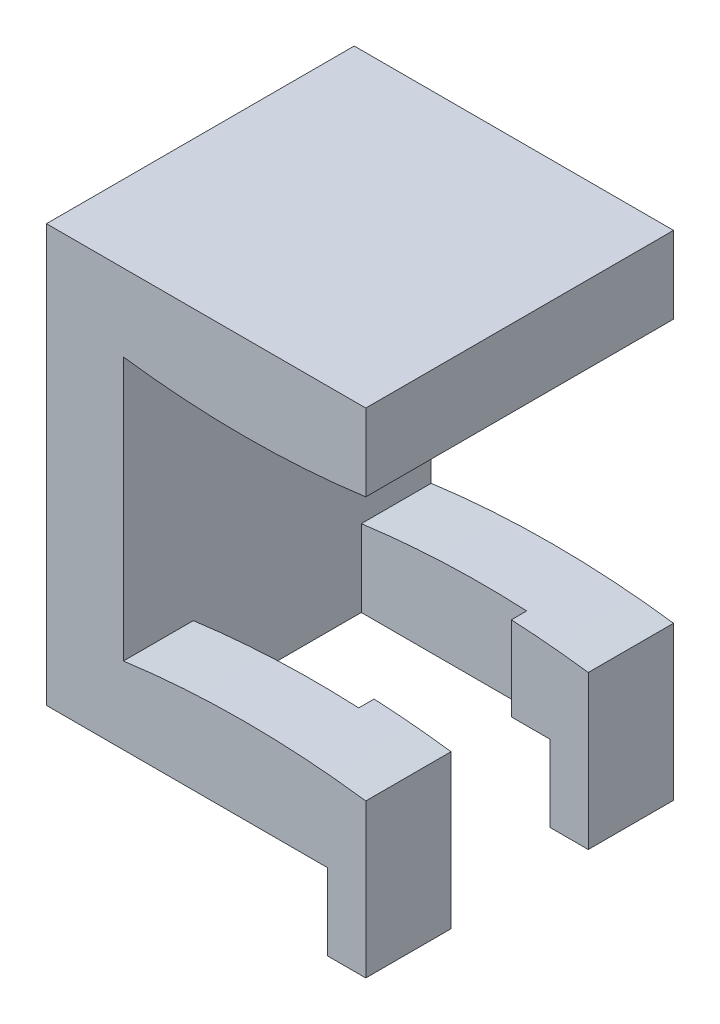
SolidWorks part; units mm, degrees
ref_plane "Front Plane" through (0, 0, 0) normal (0, 0, 1) x (1, 0, 0)
ref_plane "Top Plane" through (0, 0, 0) normal (0, 1, 0) x (1, 0, 0)
ref_plane "Right Plane" through (0, 0, 0) normal (1, 0, 0) x (0, 0, -1)
sketch "Sketch1" plane through (0, 0, 0) normal (0, 0, 1) x (1, 0, 0)
  line L2 (-159.7982, 8.1335) -> (-172.2482, 8.1335)
  line L3 (-172.2482, 8.1335) -> (-172.2482, -8.1335)
  line L7 (-169.2482, -22.8519) -> (-169.2482, 5.1335) construction
  line L12 (-169.2482, 4.7625) -> (-169.2482, 1.5875) construction
  line L23 (-159.7982, 5.1335) -> (-159.7982, 8.1335)
  line L28 (-164.5232, 4.8125) -> (-144.5007, 4.8125) construction
  line L29 (-156.5482, 4.7625) -> (-169.2482, 4.7625) construction
  line L30 (-169.2482, 5.1335) -> (-169.2482, 4.7625)
  line L32 (-158.1026, 4.7625) -> (-158.1026, -4.7625) construction
  line L33 (-169.2482, -4.7625) -> (-156.5482, -4.7625) construction
  line L34 (-169.2482, 4.7625) -> (-169.2482, -4.7625)
  line L35 (-172.2482, 0) -> (-169.2482, 0) construction
  line L36 (-169.2482, -5.1335) -> (-169.2482, -4.7625)
  line L37 (-159.7982, -5.1335) -> (-159.7982, -8.1335)
  line L38 (-159.7982, -8.1335) -> (-172.2482, -8.1335)
  line L39 (-159.7982, 4.7625) -> (-159.7982, 1.5875) construction
  arc A5 (-169.2482, 5.1335) -> (-159.7982, 5.1335) centre (-164.5232, 39.752) ccw
  arc A6 (-169.2482, -5.1335) -> (-159.7982, -5.1335) centre (-164.5232, -39.752) cw
  point P18 (-158.1026, 0)
  dimension "D4" = 3
  dimension "D3" = 3
  dimension "D1" = 0.05
extrude "MainBody" add sketch "Sketch1" along normal mid plane 12
sketch "Sketch2" plane through (0, -8.1335, 0) normal (0, -1, 0) x (1, 0, 0)
  line L11 (-162.7982, -2.675) -> (-159.7982, -2.675)
  line L12 (-162.7982, -3.275) -> (-162.7982, -2.675)
  line L13 (-169.2482, -3.275) -> (-162.7982, -3.275)
  line L14 (-162.8982, 3.175) -> (-169.2482, 3.175) construction
  line L19 (-169.2482, 3.275) -> (-162.7982, 3.275)
  line L20 (-169.2482, 6) -> (-169.2482, -6) construction
  line L21 (-162.7982, 3.275) -> (-162.7982, 2.675)
  line L22 (-162.7982, 2.675) -> (-159.7982, 2.675)
  line L23 (-159.7982, 2.675) -> (-159.7982, -2.675)
  line L24 (-169.2482, 3.275) -> (-169.2482, -3.275)
  line L25 (-169.2482, -63.5) -> (-169.2482, 63.5) construction
  line L26 (-169.2482, 0) -> (-159.7982, 0) construction
  line L27 (-162.8982, -3.175) -> (-162.8982, 3.175) construction
  line L28 (-159.7982, 6) -> (-159.7982, -6) construction
  dimension "D1" = 0.1
  dimension "D2" = 0.1
  dimension "D3" = 0.5
extrude "Grip" cut sketch "Sketch2" against normal up to next
sketch "Sketch3" plane through (0, -8.1335, 0) normal (0, -1, 0) x (1, 0, 0)
  line L0 (-159.7982, 2.675) -> (-162.7982, 2.675) construction
  line L1 (-159.7982, 6) -> (-161.2982, 6)
  line L2 (-159.7982, 6) -> (-159.7982, 2.675)
  line L3 (-159.7982, 2.675) -> (-161.2982, 2.675)
  line L4 (-161.2982, 6) -> (-161.2982, 2.675)
  line L5 (-172.2482, 0) -> (-159.7982, 0) construction
  line L6 (-172.2482, 6) -> (-172.2482, -6) construction
  line L7 (-159.7982, 6) -> (-159.7982, -6) construction
  line L8 (-159.7982, -2.675) -> (-161.2982, -2.675)
  line L9 (-159.7982, -6) -> (-159.7982, -2.675)
  line L10 (-159.7982, -6) -> (-161.2982, -6)
  line L11 (-161.2982, -6) -> (-161.2982, -2.675)
extrude "Boss-Extrude1" add sketch "Sketch3" along normal up to surface (2.979 mm away)
equation "\"HookThickness\"=3"
equation "\"HookOverhang\"=3"
equation "\"HookHeight\"=5"
equation "\"D3@Sketch1\"=\"HookThickness\""
equation "\"D4@Sketch1\"=\"HookThickness\""
equation "\"D1@Sketch2\"=0.1mm"
equation "\"D2@Sketch2\"=0.1mm"
equation "\"D3@Sketch2\"=0.5mm"
